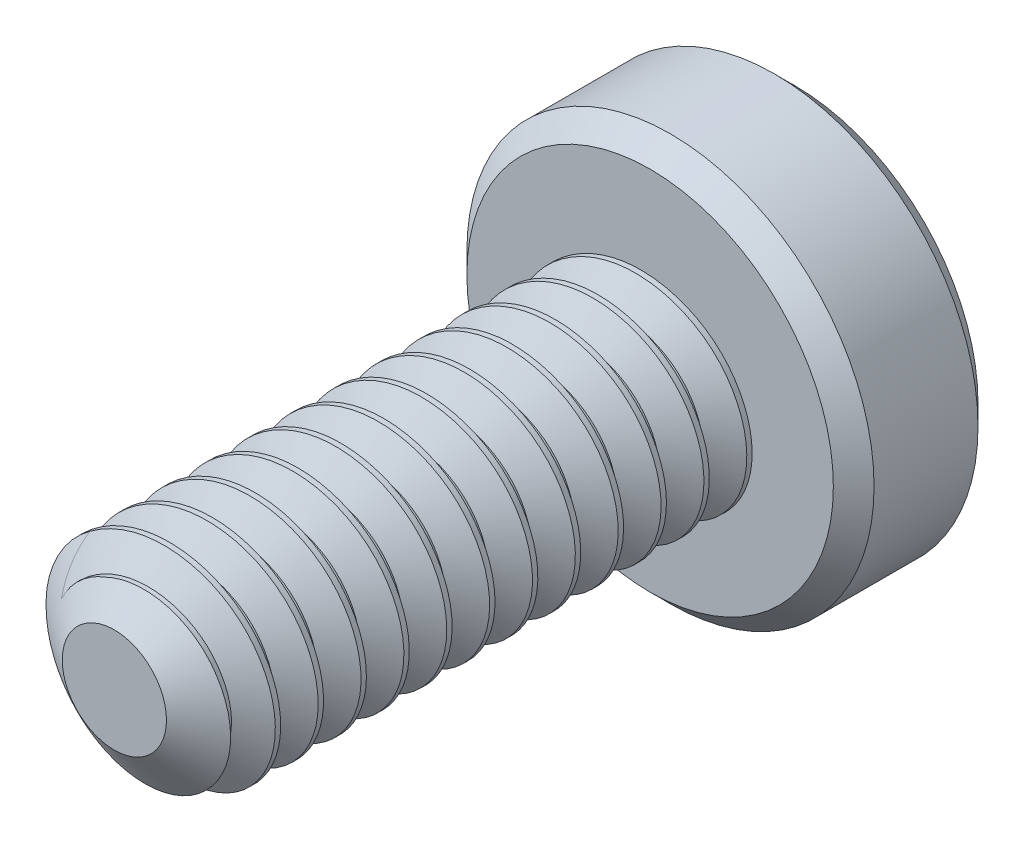
SolidWorks part; units mm, degrees
other "DetailItem1"
ref_plane "Front Plane" through (0, 0, 0) normal (0, 0, 1) x (1, 0, 0)
ref_plane "Top Plane" through (0, 0, 0) normal (0, 1, 0) x (1, 0, 0)
ref_plane "Right Plane" through (0, 0, 0) normal (1, 0, 0) x (0, 0, -1)
sketch "Sketch1" plane through (0, 0, 0) normal (0, 0, 1) x (1, 0, 0)
  circle A0 centre (0, 0) radius 1
  dimension "OD" = 2
extrude "Extrude1" add sketch "Sketch1" against normal blind 5
sketch "Sketch2" plane through (0, 0, 0) normal (0, 0, 1) x (1, 0, 0)
  circle A0 centre (0, 0) radius 1 construction
  circle A1 centre (0, 0) radius 1
curve "Helix/Spiral1" pitch 0.4 height 5.4 radius 1 centre (0, 0, 0) axis (0, 0, -1) start towards (0, 1, 0) parameters "pitch"=0.4
sketch "Sketch3" plane through (0, 0, 0) normal (1, 0, 0) x (0, 0, -1)
  line L0 (-0.35, 1) -> (-0.2, 0.7402)
  line L1 (-0.2, 0.7402) -> (-0.15, 0.7402)
  line L2 (-0.15, 0.7402) -> (0, 1)
  line L3 (-0.35, 1) -> (0, 1)
  line L4 (-0.175, 1) -> (-0.175, 0.7402) construction
  line L5 (-0.275, 0.8701) -> (-0.075, 0.8701) construction
  line L6 (0, 1) -> (0, -1) construction
  dimension "D1" = 0.05
  dimension "D2" = 0.2
  dimension "D3" = 60
sweep "Cut-Sweep1" cut profiles "Sketch3" path "Helix/Spiral1" align with end faces yes
sketch "Sketch4" plane through (0, 0, 0) normal (1, 0, 0) x (0, 0, -1)
  line L0 (0.3598, 1) -> (0, 0.4862)
  line L1 (0, 0.4862) -> (0, 1)
  line L2 (0.3598, 1) -> (0, 1)
  line L3 (-0.35, 1) -> (0, 1) construction
  line L4 (0, 0) -> (7.0209, 0) construction
  dimension "D1" = 55
  dimension "D2" = 0.254
revolve "Cut-Revolve1" cut sketch "Sketch4" angle 360 about L4
sketch "Sketch6" plane through (0, 0, -5) normal (0, 0, -1) x (-1, 0, 0)
  circle A0 centre (0, 0) radius 1.9
  dimension "head dia" = 3.8
extrude "Extrude2" add sketch "Sketch6" along normal blind 1.35
sketch "Sketch7" plane through (0, 0, -6.35) normal (0, 0, -1) x (-1, 0, 0)
  line L1 (0, 0.7506) -> (-0.65, 0.3753)
  line L2 (-0.65, 0.3753) -> (-0.65, -0.3753)
  line L3 (-0.65, -0.3753) -> (0, -0.7506)
  line L4 (0, -0.7506) -> (0.65, -0.3753)
  line L5 (0.65, -0.3753) -> (0.65, 0.3753)
  line L6 (0.65, 0.3753) -> (0, 0.7506)
  circle A0 centre (0, 0) radius 0.65 construction
  dimension "hex dia" = 1.3
extrude "Cut-Extrude1" cut sketch "Sketch7" against normal blind 0.975
sketch "Sketch8" plane through (0, 0, -6.35) normal (0, 0, -1) x (-1, 0, 0)
  circle A0 centre (0, 0) radius 0.7506
extrude "Cut-Extrude2" cut sketch "Sketch8" against normal through all draft 45
chamfer "Chamfer1" distance 0.19 angle 45 2 edges at (-1.9, 0, -6.35) (-1.9, 0, -5)
sketch "Sketch10" plane through (0, 0, -5) normal (0, 0, 1) x (1, 0, 0)
  circle A1 centre (0, 0) radius 1
  circle A2 centre (0, 0) radius 1
  dimension "D1" = 0
ref_plane "Plane1" through (0, 0, -30) normal (0, 0, 1) x (1, 0, 0)
extrude "partial thread" [suppressed] add sketch "Sketch10" along normal up to surface (10 mm away) separate body up to plane "Plane1"
chamfer "Chamfer2" [suppressed] distance 0.04 angle 45
combine bodies "Combine1" [suppressed] operation type add bodies to combine 107 108
sketch "Sketch9" plane through (0, 0, 0) normal (1, 0, 0) x (0, 0, -1)
  line L0 (0, 1) -> (0, -1) construction
  line L1 (1, 1) -> (1, -1) construction
  dimension "D1" = 1
equation "\"D3@Helix/Spiral1\" = \"screw length@Extrude1\"+\"pitch@Helix/Spiral1\""
equation "\"D1@Sketch3\" = \"pitch@Helix/Spiral1\"*.125"
equation "\"D2@Sketch3\" = \"pitch@Helix/Spiral1\"*.5"
equation "\"D1@Cut-Extrude1\" = \"hex dia@Sketch7\"*.75"
equation "\"D1@Chamfer1\" = \"head dia@Sketch6\"*.05"
equation "\"D1@Sketch9\" = \"pitch@Helix/Spiral1\"*2.5"
equation "\"D1@Chamfer2\"=\"OD@Sketch1\"*.02"
